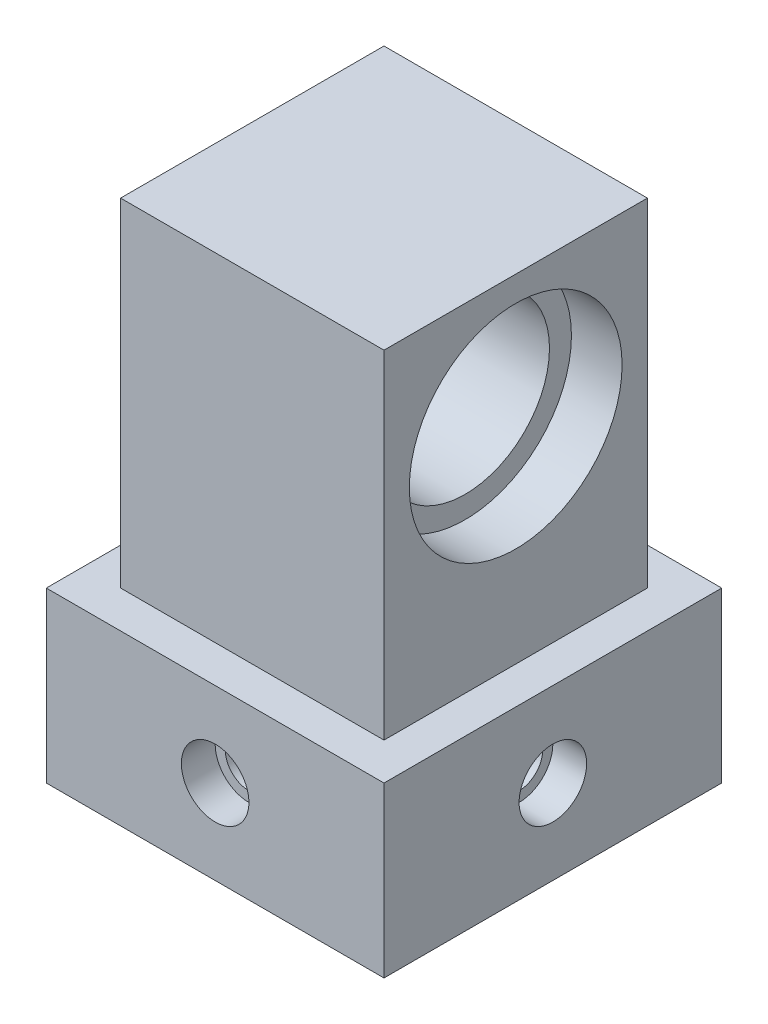
SolidWorks part; units mm, degrees
ref_plane "前视基准面" through (0, 0, 0) normal (0, 0, 1) x (1, 0, 0)
ref_plane "上视基准面" through (0, 0, 0) normal (0, 1, 0) x (1, 0, 0)
ref_plane "右视基准面" through (0, 0, 0) normal (1, 0, 0) x (0, 0, -1)
other "Configuration Table"
sketch "草图1" plane through (0, 0, 0) normal (0, 1, 0) x (1, 0, 0)
  line L1 (-3.1, -3.1) -> (3.1, -3.1)
  line L2 (-3.1, -3.1) -> (-3.1, 3.1)
  line L3 (-3.1, 3.1) -> (3.1, 3.1)
  line L4 (3.1, -3.1) -> (3.1, 3.1)
  line L5 (-3.1, -3.1) -> (3.1, 3.1) construction
  line L6 (-3.1, 3.1) -> (3.1, -3.1) construction
  line L7 (-5, -5) -> (5, -5)
  line L8 (-5, -5) -> (-5, 5)
  line L9 (-5, 5) -> (5, 5)
  line L10 (5, -5) -> (5, 5)
  line L11 (-5, -5) -> (5, 5) construction
  line L12 (-5, 5) -> (5, -5) construction
  circle A0 centre (0, 0) radius 1.25
  dimension "D2" = 2.5
  dimension "D1" = 6.2
  dimension "D3" = 10
extrude "凸台-拉伸1" add sketch "草图1" along normal blind 4 contours L7 L10 L9 L8 L4 L1 L2 L3 | A0 region at (-4.8586, 0, 0)
extrude "凸台-拉伸2" add sketch "草图1<3>" along normal blind 1 from surface contours L8 L9 L10 L7 starting at face at (0, 4, 0)
sketch "草图1<3>" plane through (0, 0, 0) normal (0, 1, 0) x (1, 0, 0) same geometry as "草图1"
sketch "草图2" plane through (0, 5, 0) normal (0, 1, 0) x (1, 0, 0)
  line L1 (-3.9, -3.9) -> (3.9, -3.9)
  line L2 (-3.9, -3.9) -> (-3.9, 3.9)
  line L3 (-3.9, 3.9) -> (3.9, 3.9)
  line L4 (3.9, -3.9) -> (3.9, 3.9)
  line L5 (-3.9, -3.9) -> (3.9, 3.9) construction
  line L6 (-3.9, 3.9) -> (3.9, -3.9) construction
  point P0 (0, 0)
  dimension "D1" = 7.8
  dimension "D2" = 7.8
extrude "凸台-拉伸3" add sketch "草图2" along normal blind 10 contours L4 L3 L2 L1
sketch "草图3" plane through (3.9, 0, 0) normal (1, 0, 0) x (0, 0, -1)
  line L0 (-3.9, 15) -> (3.9, 15) construction
  circle A0 centre (0, 11.1) radius 3.15
  circle A1 centre (0, 11.1) radius 2.5
  point P3 (0, 0)
  dimension "D2" = 6.3
  dimension "D3" = 5
  dimension "D1" = 3.9
extrude "切除-拉伸1" cut sketch "草图3" against normal through all contours A1
extrude "切除-拉伸2" cut sketch "草图3<3>" against normal blind 1.5 contours A0 A1 region at (3.9, 11.1, 3.0609)
sketch "草图3<3>" plane through (3.9, 0, 0) normal (1, 0, 0) x (0, 0, -1) same geometry as "草图3"
extrude "切除-拉伸3" cut sketch "草图3<4>" along normal blind 1.5 from surface contours A0 A1 region at (3.9, 11.1, 3.0609) starting at face at (-3.9, 11.1, 2.5)
sketch "草图3<4>" plane through (3.9, 0, 0) normal (1, 0, 0) x (0, 0, -1) same geometry as "草图3"
sketch "草图4" plane through (5, 0, 0) normal (1, 0, 0) x (0, 0, -1)
  line L0 (0, 5) -> (0, 0) construction
  line L1 (-3.9, 5) -> (3.9, 5) construction
  circle A0 centre (0, 2.5) radius 1
  circle A1 centre (0, 2.5) radius 0.7
  point P8 (0, 0)
  dimension "D1" = 2
  dimension "D2" = 1.4
extrude "切除-拉伸4" cut sketch "草图4" against normal blind 1
extrude "切除-拉伸5" cut sketch "草图4<2>" along normal blind 1 from surface starting at face at (-5, 2.5, 0)
sketch "草图4<2>" plane through (5, 0, 0) normal (1, 0, 0) x (0, 0, -1) same geometry as "草图4"
extrude "切除-拉伸6" cut sketch "草图4<3>" against normal up to next contours A1
sketch "草图4<3>" plane through (5, 0, 0) normal (1, 0, 0) x (0, 0, -1) same geometry as "草图4"
extrude "切除-拉伸7" cut sketch "草图4<4>" along normal up to next from surface contours A1 starting at face at (-5, 2.5, 1)
sketch "草图4<4>" plane through (5, 0, 0) normal (1, 0, 0) x (0, 0, -1) same geometry as "草图4"
sketch "草图5" plane through (0, 0, -5) normal (0, 0, -1) x (-1, 0, 0)
  line L0 (0, 5) -> (0, 0) construction
  line L1 (-5, 5) -> (5, 5) construction
  line L2 (5, 0) -> (-5, 0) construction
  circle A0 centre (0, 2.5) radius 1
  circle A1 centre (0, 2.5) radius 0.7
  point P9 (0, 0)
  dimension "D1" = 2
  dimension "D2" = 1.4
extrude "切除-拉伸8" cut sketch "草图5" against normal up to next contours A1
extrude "切除-拉伸9" cut sketch "草图5<3>" along normal up to next from surface contours A1 starting at face at (0, 2.5, 5)
sketch "草图5<3>" plane through (0, 0, -5) normal (0, 0, -1) x (-1, 0, 0) same geometry as "草图5"
extrude "切除-拉伸10" cut sketch "草图5<4>" against normal blind 1 contours A0
sketch "草图5<4>" plane through (0, 0, -5) normal (0, 0, -1) x (-1, 0, 0) same geometry as "草图5"
extrude "切除-拉伸11" cut sketch "草图5<5>" along normal blind 1 from surface contours A0 starting at face at (-0.7, 2.5, 5)
sketch "草图5<5>" plane through (0, 0, -5) normal (0, 0, -1) x (-1, 0, 0) same geometry as "草图5"
